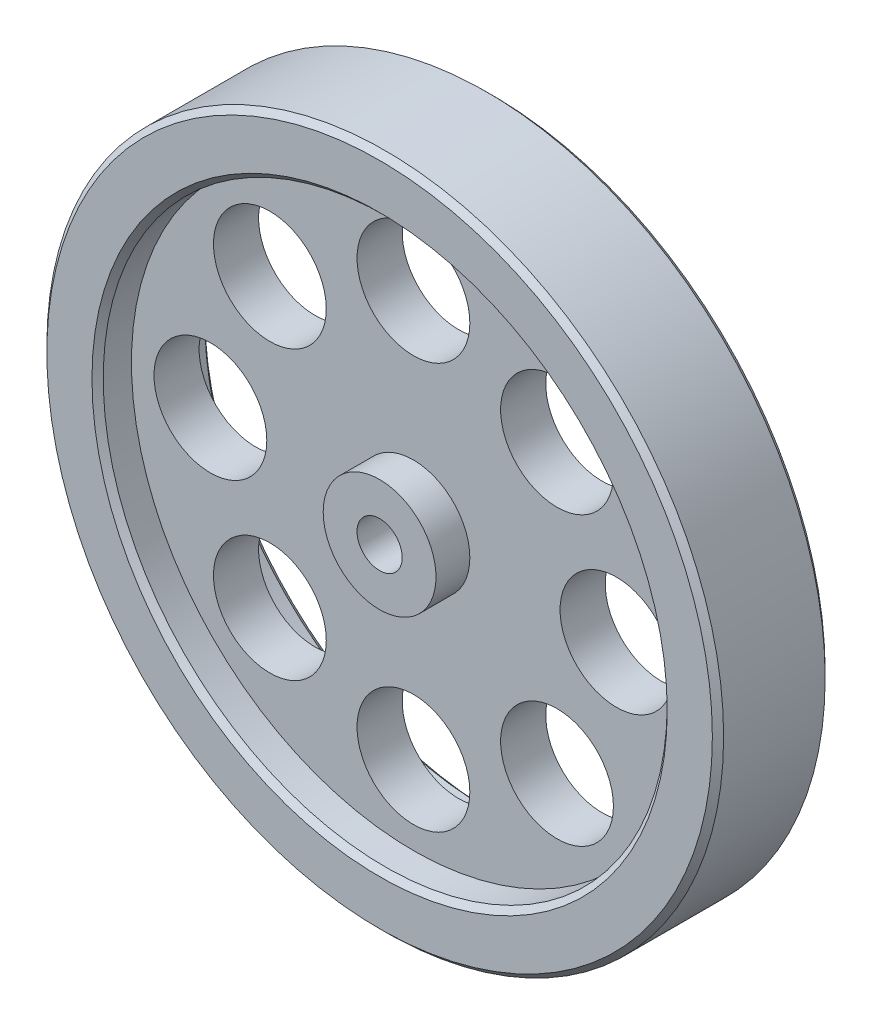
SolidWorks part; units mm, degrees
ref_plane "Front Plane" through (0, 0, 0) normal (0, 0, 1) x (1, 0, 0)
ref_plane "Top Plane" through (0, 0, 0) normal (0, 1, 0) x (1, 0, 0)
ref_plane "Right Plane" through (0, 0, 0) normal (1, 0, 0) x (0, 0, -1)
sketch "Sketch1" plane through (0, 0, 0) normal (0, 0, 1) x (1, 0, 0)
  circle A0 centre (0, 0) radius 30
  circle A1 centre (0, 0) radius 25
  dimension "D1" = 60
  dimension "D2" = 50
extrude "Boss-Extrude1" add sketch "Sketch1" along normal mid plane 10
sketch "Sketch2" plane through (0, 0, 0) normal (0, 0, 1) x (1, 0, 0)
  circle A0 centre (0, 0) radius 25 construction
  circle A1 centre (0, 0) radius 25
  circle A2 centre (0, 0) radius 5
  dimension "D1" = 10
extrude "Boss-Extrude2" add sketch "Sketch2" along normal mid plane 4 contours A1
extrude "Cut-Extrude1" cut sketch "Sketch2<4>" against normal through all both and the other way through all contours A2
sketch "Sketch2<4>" plane through (0, 0, 0) normal (0, 0, 1) x (1, 0, 0) same geometry as "Sketch2"
sketch "Sketch3" plane through (0, 0, -2) normal (0, 0, -1) x (-1, 0, 0)
  circle A0 centre (0, 0) radius 5 construction
  circle A1 centre (0, 0) radius 5
  circle A2 centre (0, 0) radius 2
  dimension "D1" = 4
extrude "Boss-Extrude3" add sketch "Sketch3" along normal blind 3 and the other way blind 7
sketch "Sketch4" plane through (0, 0, -2) normal (0, 0, -1) x (-1, 0, 0)
  circle A0 centre (0, 18) radius 5
  circle A1 centre (12.7279, 12.7279) radius 5
  circle A2 centre (18, 0) radius 5
  circle A3 centre (12.7279, -12.7279) radius 5
  circle A4 centre (0, -18) radius 5
  circle A5 centre (-12.7279, -12.7279) radius 5
  circle A6 centre (-18, 0) radius 5
  circle A7 centre (-12.7279, 12.7279) radius 5
  point P19 (0, 0)
  dimension "D1" = 10
  dimension "D2" = 18
  dimension "D3" = 8
extrude "Cut-Extrude2" cut sketch "Sketch4" against normal through all both and the other way through all
chamfer "Chamfer1" distance 0.5 angle 45 4 edges at (25, 0, 5) (30, 0, 5) (25, 0, -5) (30, 0, -5)
